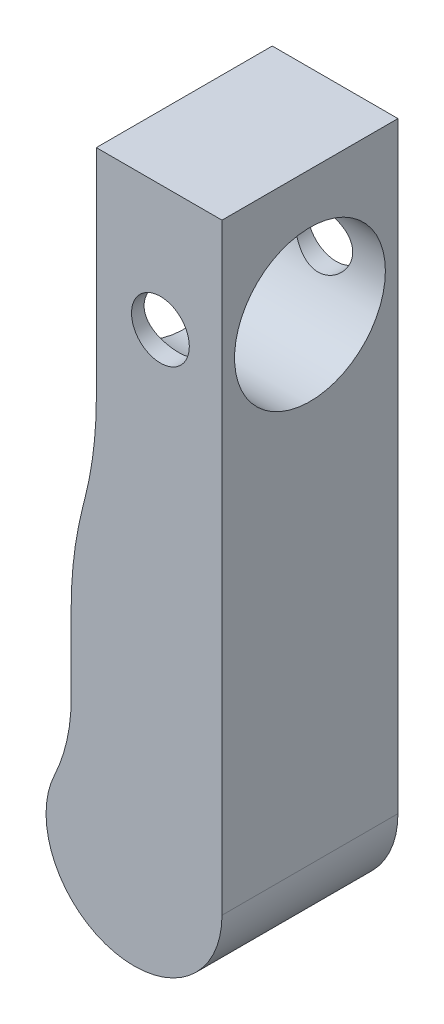
SolidWorks part; units mm, degrees
ref_plane "Plan de face" through (0, 0, 0) normal (0, 0, 1) x (1, 0, 0)
ref_plane "Plan de dessus" through (0, 0, 0) normal (0, 1, 0) x (1, 0, 0)
ref_plane "Plan de droite" through (0, 0, 0) normal (1, 0, 0) x (0, 0, -1)
sketch "Esquisse1" plane through (0, 0, 0) normal (0, 0, 1) x (1, 0, 0)
  line L2 (-5, 0) -> (-5, -10.5)
  line L5 (-5, 0) -> (0, 0)
  line L10 (-6, -14.5) -> (-6, -21.5)
  line L13 (-6, -14.5) -> (-5, -10.5)
  line L14 (-3.5, -23.9495) -> (0, -23.9495) construction
  line L15 (0, 0) -> (0, -23.9495)
  arc A1 (-6, -21.5) -> (0, -23.9495) centre (-3.5, -23.9495) ccw
  dimension "D5" = 7
  dimension "D1" = 5
  dimension "D2" = 10.5
  dimension "D3" = 4
  dimension "D4" = 1
  dimension "D6" = 7
  dimension "D8" = 3.5
  dimension "D9" = 3.5
extrude "Boss.-Extru.2" add sketch "Esquisse1" along normal blind 7 contours L13 L2 L5 L15 A1 L10
fillet "Congé1" radius 7 1 edges at (-6, -21.5, 3.5)
fillet "Congé2" radius 15 2 edges at (-6, -14.5, 3.5) (-5, -10.5, 3.5)
sketch "Esquisse4" plane through (0, 0, 7) normal (0, 0, 1) x (1, 0, 0)
  line L0 (0, 0) -> (0, -23.9495) construction
  line L1 (-5, 0) -> (0, 0) construction
  point P0 (-2.45, -5)
  dimension "D1" = 2.45
  dimension "D2" = 5
hole_wizard "Ø2.3 (2.3) Diameter Hole1" positions "Esquisse4" profile "Esquisse3" hole size "Ø2.3" standard "ANSI Metric" end condition through all
sketch "Esquisse3" plane through (-2.45, -5, 7) normal (1, 0, 0) x (0, -1, 0)
  line L0 (0, 0) -> (0, 7)
  line L1 (0, 7) -> (1.15, 7)
  line L2 (1.15, 7) -> (1.15, 0)
  line L5 (1.15, 0) -> (0, 0)
  line L11 (0, -6.35) -> (0, 107.95) construction
  dimension "Diamètre du perçage jusqu'au prochain" = 2.3
  dimension "Profondeur du perçage jusqu'au prochain" = 7
sketch "Esquisse7" plane through (0, 0, 0) normal (1, 0, 0) x (0, 0, -1)
  line L2 (-7, 0) -> (0, 0) construction
  point P0 (-3.5, -5)
  point P7 (-3.5, 0)
  dimension "D1" = 5
hole_wizard "Ø6.0 (6) Diameter Hole1" positions "Esquisse7" profile "Esquisse6" hole size "Ø6.0" standard "ANSI Metric" end condition through all
sketch "Esquisse6" plane through (0, -5, 3.5) normal (0, 1, 0) x (0, 0, -1)
  line L0 (0, 0) -> (0, 7)
  line L1 (0, 7) -> (3, 7)
  line L2 (3, 7) -> (3, 0)
  line L5 (3, 0) -> (0, 0)
  line L11 (0, -6.35) -> (0, 107.95) construction
  dimension "Diamètre du perçage jusqu'au prochain" = 6
  dimension "Profondeur du perçage jusqu'au prochain" = 7
